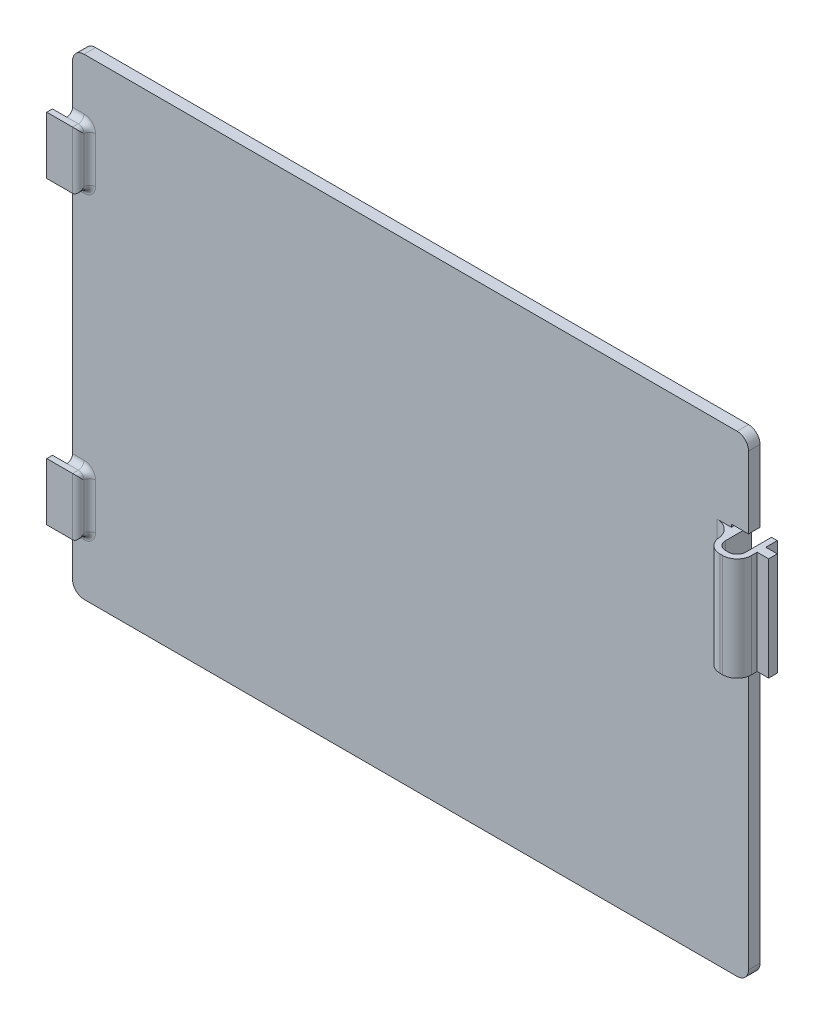
SolidWorks part; units mm, degrees
ref_plane "Front Plane" through (0, 0, 0) normal (0, 0, 1) x (1, 0, 0)
ref_plane "Top Plane" through (0, 0, 0) normal (0, 1, 0) x (1, 0, 0)
ref_plane "Right Plane" through (0, 0, 0) normal (1, 0, 0) x (0, 0, -1)
sketch "Sketch1" plane through (0, 0, 0) normal (0, 0, 1) x (1, 0, 0)
  line L1 (58.875, -41.125) -> (-58.875, -41.125)
  line L2 (58.875, -41.125) -> (58.875, 41.125)
  line L3 (58.875, 41.125) -> (-58.875, 41.125)
  line L4 (-58.875, -41.125) -> (-58.875, 41.125)
  line L5 (58.875, -41.125) -> (-58.875, 41.125) construction
  line L6 (58.875, 41.125) -> (-58.875, -41.125) construction
  point P0 (0, 0)
  dimension "D1" = 117.75
  dimension "D2" = 82.25
extrude "body" add sketch "Sketch1" along normal blind 2
sketch "Sketch2" plane through (0, 0, 2) normal (0, 0, 1) x (1, 0, 0)
  line L0 (-58.875, 41.125) -> (-58.875, -41.125) construction
  line L1 (-58.875, 31.125) -> (-55.875, 31.125)
  line L2 (-58.875, 31.125) -> (-58.875, 21.125)
  line L3 (-58.875, 21.125) -> (-55.875, 21.125)
  line L4 (-55.875, 31.125) -> (-55.875, 21.125)
  line L5 (58.875, 41.125) -> (-58.875, 41.125) construction
  line L6 (-58.875, -21.125) -> (-55.875, -21.125)
  line L7 (-58.875, -21.125) -> (-58.875, -31.125)
  line L8 (-58.875, -31.125) -> (-55.875, -31.125)
  line L9 (-55.875, -21.125) -> (-55.875, -31.125)
  line L10 (-58.875, -41.125) -> (58.875, -41.125) construction
  dimension "D1" = 10
  dimension "D2" = 10
  dimension "D3" = 3
  dimension "D4" = 10
  dimension "D5" = 10
  dimension "D6" = 3
extrude "clip_mounts" add sketch "Sketch2" along normal blind 2
sketch "Sketch3" plane through (-58.875, 0, 0) normal (-1, 0, 0) x (0, 0, 1)
  line L0 (4, 21.125) -> (2, 21.125) construction
  line L1 (4, 31.125) -> (3, 31.125)
  line L2 (4, 31.125) -> (4, 21.125)
  line L3 (4, 21.125) -> (3, 21.125)
  line L4 (3, 31.125) -> (3, 21.125)
  line L13 (4, -21.125) -> (2, -21.125) construction
  line L14 (4, -31.125) -> (3, -31.125)
  line L15 (4, -31.125) -> (4, -21.125)
  line L16 (4, -21.125) -> (3, -21.125)
  line L17 (3, -31.125) -> (3, -21.125)
  dimension "D1" = 1
  dimension "D2" = 1
extrude "clips" add sketch "Sketch3" along normal blind 2.5
sketch "Sketch4" plane through (0, 0, 2) normal (0, 0, 1) x (1, 0, 0)
  line L0 (58.875, -41.125) -> (58.875, 41.125) construction
  line L1 (58.875, 26.625) -> (56.375, 26.625)
  line L2 (58.875, 26.625) -> (58.875, 7.625)
  line L3 (58.875, 7.625) -> (56.375, 7.625)
  line L4 (56.375, 26.625) -> (56.375, 7.625)
  line L5 (58.875, 41.125) -> (-58.875, 41.125) construction
  dimension "D1" = 14.5
  dimension "D2" = 2.5
  dimension "D6" = 19
extrude "holder" add sketch "Sketch4" along normal blind 5
sketch "Sketch7" plane through (58.875, 0, 0) normal (1, 0, 0) x (0, 0, -1)
  line L5 (0, -41.125) -> (0, 41.125) construction
  line L10 (-7, 7.625) -> (0, 7.625)
  line L11 (-7, 7.625) -> (-7, 26.625)
  line L12 (-7, 26.625) -> (0, 26.625)
  line L13 (0, 7.625) -> (0, 26.625)
  dimension "D1" = 19
extrude "holder_ext" add sketch "Sketch7" along normal blind 3
sketch "Sketch8" plane through (61.875, 0, 0) normal (1, 0, 0) x (0, 0, -1)
  line L1 (-7, 26.625) -> (3, 26.625)
  line L2 (-7, 26.625) -> (-7, 26.125)
  line L3 (-7, 26.125) -> (3, 26.125)
  line L4 (3, 26.625) -> (3, 26.125)
  line L5 (-7, 7.625) -> (3, 7.625)
  line L6 (-7, 7.625) -> (-7, 8.125)
  line L7 (-7, 8.125) -> (3, 8.125)
  line L8 (3, 7.625) -> (3, 8.125)
  dimension "D1" = 0.5
  dimension "D2" = 0.5
  dimension "D5" = 10
  dimension "D6" = 10
extrude "holder_cut" cut sketch "Sketch8" against normal blind 6
sketch "Sketch10" plane through (0, 0, 0) normal (0, 0, -1) x (-1, 0, 0)
  line L6 (-55.875, 8.125) -> (-61.875, 8.125) construction
  line L7 (-60.875, 8.125) -> (-57.375, 8.125)
  line L8 (-60.875, 8.125) -> (-60.875, 26.125)
  line L9 (-60.875, 26.125) -> (-57.375, 26.125)
  line L10 (-57.375, 8.125) -> (-57.375, 26.125)
  line L11 (-55.875, 26.125) -> (-61.875, 26.125) construction
  line L14 (-58.875, 26.625) -> (-58.875, 41.125) construction
  dimension "D1" = 3.5
  dimension "D2" = 2
extrude "holder_remove" cut sketch "Sketch10" against normal blind 6
fillet "Fillet5" radius 2 4 edges at (58.875, -41.125, 1) (58.875, 41.125, 1) (-58.875, -41.125, 1) (-58.875, 41.125, 1)
fillet "Fillet6" radius 2.5 2 edges at (61.875, 17.125, 7) (56.375, 17.125, 7)
sketch "Sketch12" plane through (61.875, 0, 0) normal (1, 0, 0) x (0, 0, -1)
  line L0 (0, 8.125) -> (-4.5, 8.125) construction
  line L1 (-2, 8.125) -> (-3.5, 8.125)
  line L2 (-2, 8.125) -> (-2, 26.125)
  line L3 (-2, 26.125) -> (-3.5, 26.125)
  line L4 (-3.5, 8.125) -> (-3.5, 26.125)
  line L5 (0, 8.125) -> (0, 26.125) construction
  dimension "D1" = 1.5
  dimension "D2" = 2
  dimension "D3" = 18
extrude "hold_pin" add sketch "Sketch12" along normal blind 2
fillet "Fillet7" radius 1 12 edges at (-57.375, 21.125, 2) (-57.375, 31.125, 2) (-57.375, -31.125, 2) (-57.375, -21.125, 2) (-55.875, 21.125, 3) (-55.875, 26.125, 4) (-55.875, 31.125, 3) (-55.875, 26.125, 2) (-55.875, -31.125, 3) (-55.875, -26.125, 4) (-55.875, -21.125, 3) (-55.875, -26.125, 2)
fillet "Fillet8" radius 3 1 edges at (56.375, 17.125, 2)
fillet "Fillet9" radius 1.5 2 edges at (57.375, 17.125, 6) (60.875, 17.125, 6)
